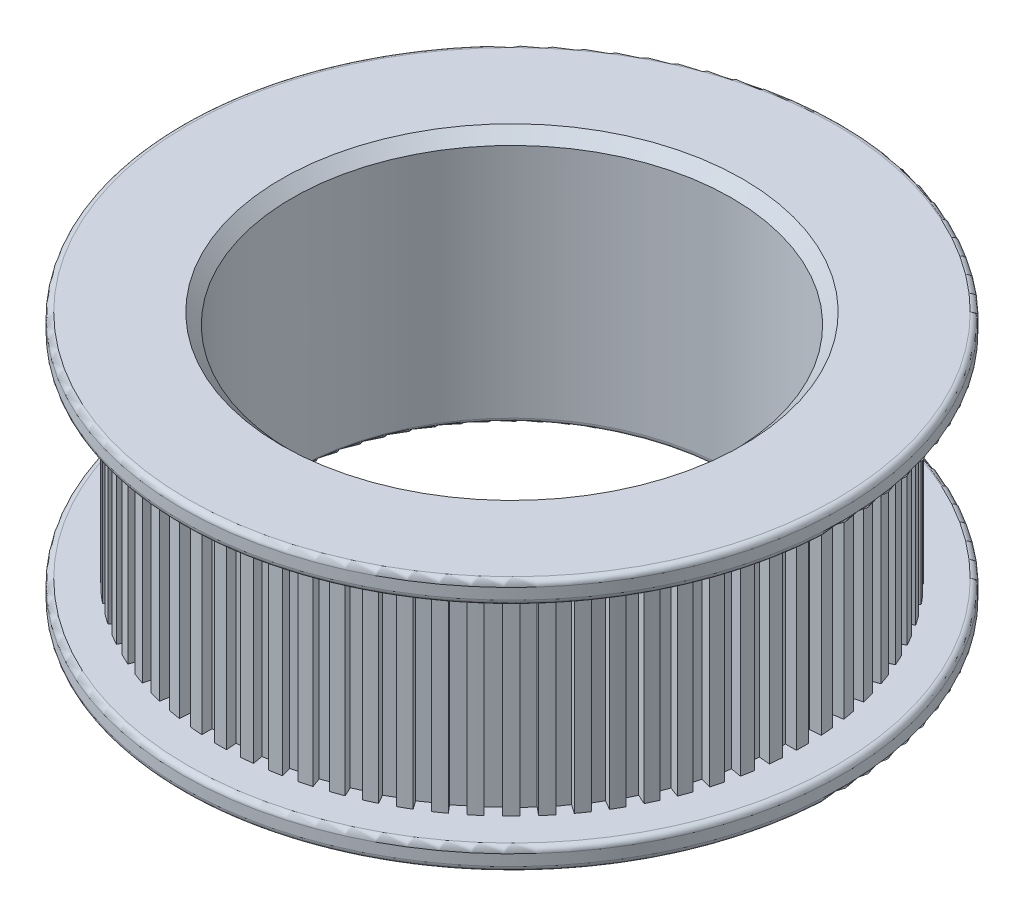
SolidWorks part; units mm, degrees
ref_plane "Front Plane" through (0, 0, 0) normal (0, 0, 1) x (1, 0, 0)
ref_plane "Top Plane" through (0, 0, 0) normal (0, 1, 0) x (1, 0, 0)
ref_plane "Right Plane" through (0, 0, 0) normal (1, 0, 0) x (0, 0, -1)
sketch "Sketch1" plane through (0, 0, 0) normal (0, 0, 1) x (1, 0, 0)
  line L0 (508, 0) -> (762, 0)
  line L1 (762, 0) -> (762, 50.8)
  line L2 (762, 50.8) -> (673.1, 50.8)
  line L3 (673.1, 50.8) -> (673.1, 533.4)
  line L4 (673.1, 533.4) -> (762, 533.4)
  line L5 (762, 533.4) -> (762, 584.2)
  line L6 (762, 584.2) -> (508, 584.2)
  line L7 (508, 584.2) -> (508, 0)
  line L8 (0, 0) -> (0, 345.2148) construction
  dimension "D1" = 508
  dimension "D2" = 254
  dimension "D3" = 254
  dimension "D4" = 50.8
  dimension "D5" = 50.8
  dimension "D6" = 584.2
  dimension "D7" = 88.9
revolve "Revolve1" add sketch "Sketch1" angle 360 about L8
chamfer "Chamfer1" distance 25.4 angle 45 1 edges at (0, 584.2, -508)
fillet "Fillet1" radius 12.7 4 edges at (0, 584.2, -762) (0, 533.4, -762) (0, 0, -762) (0, 50.8, -762)
sketch "Sketch3" plane through (0, 50.8, 0) normal (0, 1, 0) x (1, 0, 0)
  line L1 (15.24, 647.7) -> (45.72, 647.7)
  line L2 (15.24, 647.7) -> (15.24, 678.18)
  line L3 (15.24, 678.18) -> (45.72, 678.18)
  line L4 (45.72, 647.7) -> (45.72, 678.18)
  line L5 (15.24, 647.7) -> (45.72, 678.18) construction
  line L6 (15.24, 678.18) -> (45.72, 647.7) construction
  point P0 (30.48, 662.94)
  dimension "D1" = 30.48
  dimension "D2" = 30.48
  dimension "D3" = 647.7
  dimension "D4" = 15.24
extrude "Cut-Extrude1" cut sketch "Sketch3" along normal up to surface (482.6 mm away) up to face at (0, 533.4, -749.3)
pattern_circular "CirPattern1" count 72 every 5 about axis through (0, 50.8, 0) along (0, 1, 0) of "Cut-Extrude1"
fillet "Fillet2" radius 12.7 1 edges at (0, 0, -508)
